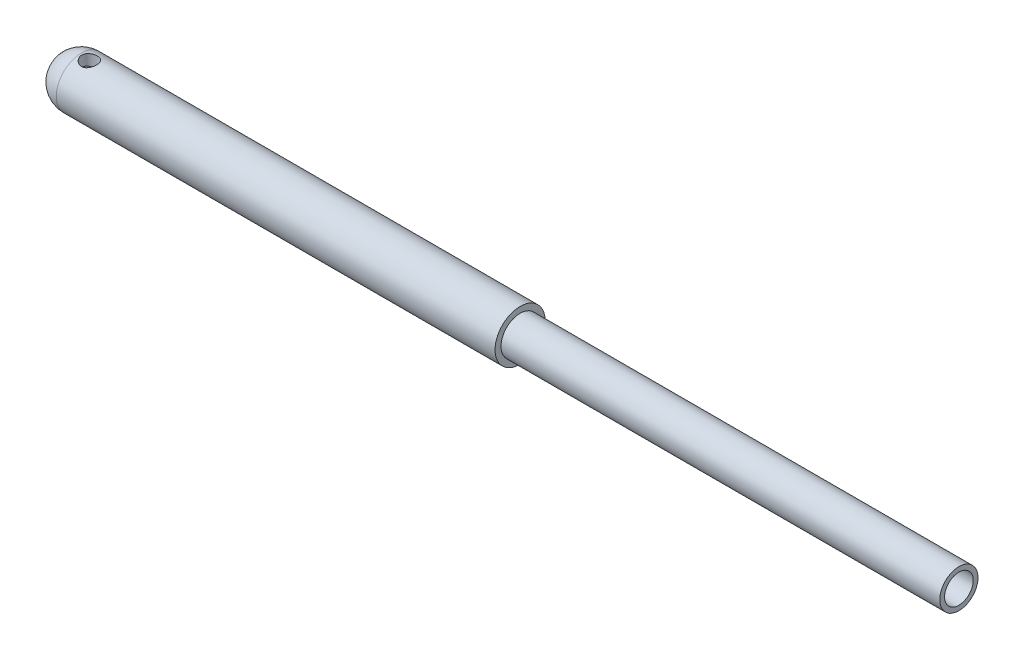
SolidWorks part; units mm, degrees
material "Alloy Steel"
ref_plane "Front Plane" through (0, 0, 0) normal (0, 0, 1) x (1, 0, 0)
ref_plane "Top Plane" through (0, 0, 0) normal (0, 1, 0) x (1, 0, 0)
ref_plane "Right Plane" through (0, 0, 0) normal (1, 0, 0) x (0, 0, -1)
ref_plane "Plane4" through (0, 13182.6176, 0) normal (0, 1, 0) x (1, 0, 0)
ref_plane "Plane5" through (0, 14236.0374, 0) normal (0, 1, 0) x (1, 0, 0)
sketch "Sketch2" plane through (0, 13182.6176, 0) normal (0, 1, 0) x (1, 0, 0)
  line L0 (23740.5019, 2266.3846) -> (30740.5019, 2266.3846)
  line L1 (24595.8074, 2114.9023) -> (18941.2507, 3116.3755) construction
  dimension "D1" = 7000
sweep "Sweep1" add path "Sketch2" circular profile diameter 304.8 parameters "D3"=304.8
sketch "Sketch31" plane through (0, 13182.6176, 0) normal (0, 1, 0) x (1, 0, 0)
  line L0 (23740.5019, 2266.3846) -> (27240.5019, 2266.3846)
  line L1 (23740.5019, 2418.7846) -> (23740.5019, 2113.9846) construction
  dimension "D1" = 3500
sweep "Sweep2" add path "Sketch31" circular profile diameter 400 parameters "D3"=400
sketch "Sketch66" plane through (0, 13182.6176, 0) normal (0, 1, 0) x (1, 0, 0)
  line L0 (23740.5019, 2466.3846) -> (23740.5019, 2066.3846) construction
  line L1 (27240.5019, 2466.3846) -> (23740.5019, 2466.3846) construction
  line L3 (23740.5019, 2066.3846) -> (27240.5019, 2066.3846) construction
  line L5 (23740.5019, 2466.3846) -> (23740.5019, 2066.3846) construction
  line L6 (23740.5019, 2466.3846) -> (23740.5019, 2066.3846)
  arc A0 (23740.5019, 2466.3846) -> (23740.5019, 2066.3846) centre (23740.5019, 2266.3846) ccw
revolve "Revolve4" add sketch "Sketch66" angle 360 about L5
sketch "Sketch99" plane through (30740.5019, 0, 0) normal (1, 0, 0) x (0, 0, -1)
  circle A2 centre (2266.3846, 13182.6176) radius 114.3
  circle A3 centre (2266.3846, 13182.6176) radius 114.3
  dimension "D1" = 38.1
extrude "Cut-Extrude1" cut sketch "Sketch99" against normal blind 7000
extrude "Cut-Extrude2" cut sketch "Sketch140" against normal mid plane 3500
sketch "Sketch140" plane through (187.7959, 14236.0374, -4220.0634) normal (0, -1, 0) x (0.9847, 0, 0.1744)
  circle A0 centre (23612.1268, -2183.7339) radius 63.5
